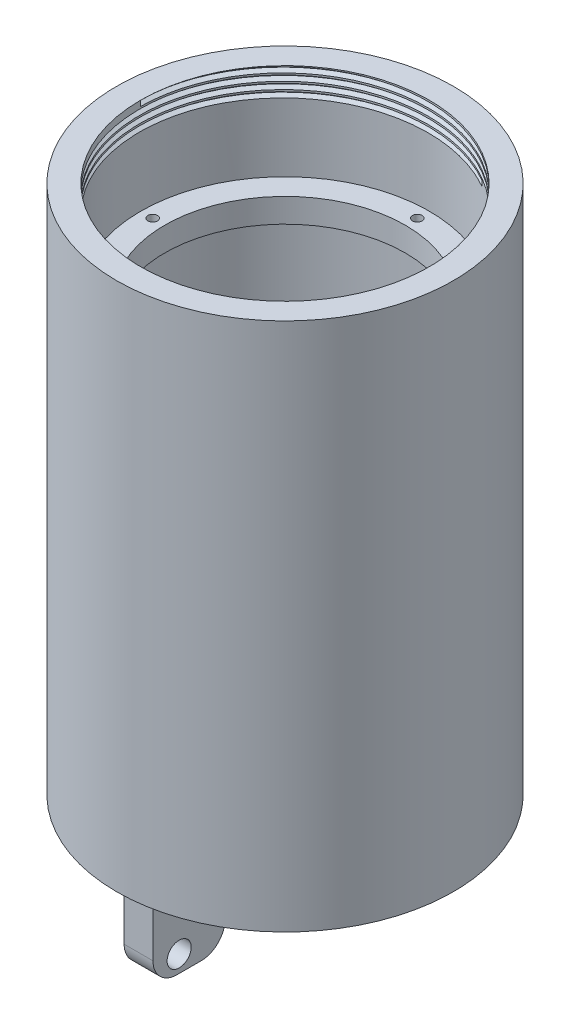
SolidWorks part; units mm, degrees
ref_plane "Front Plane" through (0, 0, 0) normal (0, 0, 1) x (1, 0, 0)
ref_plane "Top Plane" through (0, 0, 0) normal (0, 1, 0) x (1, 0, 0)
ref_plane "Right Plane" through (0, 0, 0) normal (1, 0, 0) x (0, 0, -1)
sketch "Sketch5" plane through (0, 0, 0) normal (0, 1, 0) x (1, 0, 0)
  circle A0 centre (0, 0) radius 30
  circle A1 centre (0, 0) radius 35
extrude "Boss-Extrude1" add sketch "Sketch5" along normal blind 110
sketch "Sketch15" plane through (0, 0, 0) normal (0, -1, 0) x (1, 0, 0)
  circle A0 centre (0, 0) radius 35
extrude "Boss-Extrude10" add sketch "Sketch15" against normal blind 7
sketch "Sketch16" plane through (0, 7, 0) normal (0, 1, 0) x (1, 0, 0)
  circle A0 centre (16, -15) radius 2
  circle A1 centre (16, 15) radius 2
  circle A2 centre (-16, 15) radius 2
  circle A3 centre (-16, -15) radius 2
  point P0 (0, 0)
extrude "Cut-Extrude7" cut sketch "Sketch16" against normal blind 5 contours A2
extrude "Cut-Extrude8" cut sketch "Sketch16<3>" against normal blind 5 contours A1
sketch "Sketch16<3>" plane through (0, 7, 0) normal (0, 1, 0) x (1, 0, 0) same geometry as "Sketch16"
extrude "Cut-Extrude9" cut sketch "Sketch16<4>" against normal blind 5 contours A0
sketch "Sketch16<4>" plane through (0, 7, 0) normal (0, 1, 0) x (1, 0, 0) same geometry as "Sketch16"
extrude "Cut-Extrude10" cut sketch "Sketch16<5>" against normal blind 5 contours A3
sketch "Sketch16<5>" plane through (0, 7, 0) normal (0, 1, 0) x (1, 0, 0) same geometry as "Sketch16"
sketch "Sketch17" plane through (0, 7, 0) normal (0, 1, 0) x (1, 0, 0)
  circle A0 centre (0, 0) radius 4.5
extrude "Cut-Extrude11" cut sketch "Sketch17" against normal through all
thread "Thread1" pitch 0.7 method cut profile "Thread Profile1" start angle 0, offset 0, length 5, pitch 0.7, diameter 4
ref_plane "Plane2" through (18, 2, -15) normal (0, 0, 1) x (1, 0, 0)
sketch "Thread Profile1" plane through (18, 2, -15) normal (0, 0, 1) x (1, 0, 0)
  line L0 (0, 0) -> (0, 0.7) construction
  line L1 (0, 0) -> (0.3789, 0.2187)
  line L2 (0.3789, 0.2187) -> (0.3789, 0.3062)
  line L3 (0.3789, 0.3062) -> (0, 0.525)
  line L4 (0.3789, 0.2625) -> (0, 0.2625) construction
  line L11 (0, 0) -> (0, 0.525)
  point P2 (0, 0)
  dimension "Pitch" = 0.7
  dimension "Profile_Angle" = 60
  dimension "Profile_Land" = 0.0875
  dimension "Profile_Height" = 0.3789
thread "Thread2" pitch 0.7 method cut profile "Thread Profile2" start angle 0, offset 0, length 5, pitch 0.7, diameter 4
ref_plane "Plane3" through (-14, 2, -15) normal (0, 0, 1) x (1, 0, 0)
sketch "Thread Profile2" plane through (-14, 2, -15) normal (0, 0, 1) x (1, 0, 0)
  line L0 (0, 0) -> (0, 0.7) construction
  line L1 (0, 0) -> (0.3789, 0.2187)
  line L2 (0.3789, 0.2187) -> (0.3789, 0.3062)
  line L3 (0.3789, 0.3062) -> (0, 0.525)
  line L4 (0.3789, 0.2625) -> (0, 0.2625) construction
  line L11 (0, 0) -> (0, 0.525)
  point P2 (0, 0)
  dimension "Pitch" = 0.7
  dimension "Profile_Angle" = 60
  dimension "Profile_Land" = 0.0875
  dimension "Profile_Height" = 0.3789
thread "Thread3" pitch 0.7 method cut profile "Thread Profile3" start angle 0, offset 0, length 5, pitch 0.7, diameter 4
ref_plane "Plane4" through (-14, 2, 15) normal (0, 0, 1) x (1, 0, 0)
sketch "Thread Profile3" plane through (-14, 2, 15) normal (0, 0, 1) x (1, 0, 0)
  line L0 (0, 0) -> (0, 0.7) construction
  line L1 (0, 0) -> (0.3789, 0.2187)
  line L2 (0.3789, 0.2187) -> (0.3789, 0.3062)
  line L3 (0.3789, 0.3062) -> (0, 0.525)
  line L4 (0.3789, 0.2625) -> (0, 0.2625) construction
  line L11 (0, 0) -> (0, 0.525)
  point P2 (0, 0)
  dimension "Pitch" = 0.7
  dimension "Profile_Angle" = 60
  dimension "Profile_Land" = 0.0875
  dimension "Profile_Height" = 0.3789
thread "Thread4" pitch 0.7 method cut profile "Thread Profile4" start angle 0, offset 0, length 5, pitch 0.7, diameter 4
ref_plane "Plane5" through (18, 2, 15) normal (0, 0, 1) x (1, 0, 0)
sketch "Thread Profile4" plane through (18, 2, 15) normal (0, 0, 1) x (1, 0, 0)
  line L0 (0, 0) -> (0, 0.7) construction
  line L1 (0, 0) -> (0.3789, 0.2187)
  line L2 (0.3789, 0.2187) -> (0.3789, 0.3062)
  line L3 (0.3789, 0.3062) -> (0, 0.525)
  line L4 (0.3789, 0.2625) -> (0, 0.2625) construction
  line L11 (0, 0) -> (0, 0.525)
  point P2 (0, 0)
  dimension "Pitch" = 0.7
  dimension "Profile_Angle" = 60
  dimension "Profile_Land" = 0.0875
  dimension "Profile_Height" = 0.3789
sketch "Sketch29" plane through (0, 0, 0) normal (0, -1, 0) x (1, 0, 0)
  line L0 (0, 0) -> (0, 35)
  line L1 (0, 0) -> (0, 22.9431)
  line L7 (-3, 15.4499) -> (3, 15.4499)
  line L8 (-3, 15.4499) -> (-3, 30.4363)
  line L9 (-3, 30.4363) -> (3, 30.4363)
  line L10 (3, 15.4499) -> (3, 30.4363)
  line L11 (-3, 15.4499) -> (3, 30.4363) construction
  line L12 (-3, 30.4363) -> (3, 15.4499) construction
  circle A0 centre (0, 0) radius 35 construction
extrude "Boss-Extrude13" add sketch "Sketch29" along normal blind 18.21 contours L7 L10 L9 L0 L1 | L9 L8 L7 L1 L0 region at (-1.5, 0, 22.9431) region at (1.5, 0, 22.9431)
fillet "Fillet1" radius 5 2 edges at (0, -18.21, 15.4499) (0, -18.21, 30.4363)
thread "Thread6" pitch 1.5 method cut profile "Thread Profile6" start angle 0, offset 0, length 5, pitch 1.5, diameter 60
ref_plane "Plane7" through (-30, 110, 0) normal (0, 0, 1) x (-1, 0, 0)
sketch "Thread Profile6" plane through (-30, 110, 0) normal (0, 0, 1) x (-1, 0, 0)
  line L0 (0, 0) -> (0, 1.5) construction
  line L1 (0, 0) -> (0.8119, 0.4687)
  line L2 (0.8119, 0.4687) -> (0.8119, 0.6562)
  line L3 (0.8119, 0.6562) -> (0, 1.125)
  line L4 (0.8119, 0.5625) -> (0, 0.5625) construction
  line L11 (0, 0) -> (0, 1.125)
  point P2 (0, 0)
  dimension "Pitch" = 1.5
  dimension "Profile_Angle" = 60
  dimension "Profile_Land" = 0.1875
  dimension "Profile_Height" = 0.8119
sketch "Sketch33" plane through (0, 7, 0) normal (0, 1, 0) x (1, 0, 0)
  circle A0 centre (20.68, 0) radius 3
  circle A1 centre (-23.2049, 0) radius 3
extrude "Cut-Extrude17" cut sketch "Sketch33" against normal blind 10 contours A1 | A0 region at (20.68, 7, 0) region at (-23.2049, 7, 0)
sketch "Sketch34" plane through (0, 0, 0) normal (0, 0, 1) x (1, 0, 0)
  line L0 (0, 0) -> (0, 85)
  line L6 (25, 85) -> (30, 85)
  line L7 (30, 85) -> (30, 90)
  line L8 (30, 90) -> (25, 90)
  line L9 (25, 90) -> (25, 85)
sketch "Sketch35" plane through (0, 0, 0) normal (0, 0, 1) x (1, 0, 0)
  line L0 (0, 0) -> (0, 60)
  line L1 (0, 0) -> (0, 85) construction
  line L2 (25, 65) -> (25, 60)
  line L3 (25, 60) -> (30, 60)
  line L12 (30, 60) -> (30, 65)
  line L13 (30, 65) -> (25, 65)
revolve "Revolve4" add sketch "Sketch35" angle 360 about L0
revolve "Revolve5" add sketch "Sketch34" angle 360 about L0
sketch "Sketch38" plane through (0, 65, 0) normal (0, 1, 0) x (1, 0, 0)
  line L0 (0, 0) -> (0, 27.5)
  line L1 (0, 0) -> (0, -27.5)
  line L2 (0, 0) -> (27.5, 0)
  line L4 (25, 0) -> (30, 0) construction
  line L5 (0, 0) -> (-27.5, 0)
  circle A0 centre (0, 27.5) radius 1
  circle A1 centre (27.5, 0) radius 1
  circle A2 centre (0, -27.5) radius 1
  circle A3 centre (-27.5, 0) radius 1
extrude "Cut-Extrude20" cut sketch "Sketch38" against normal blind 5 contours A0 | A1 | A2 | A3
sketch "Sketch39" plane through (0, 90, 0) normal (0, 1, 0) x (1, 0, 0)
  line L0 (0, 0) -> (27.5, 0)
  line L1 (0, 0) -> (-27.5, 0)
  line L2 (0, 0) -> (0, 27.5)
  line L3 (0, 0) -> (0, -27.5)
  circle A0 centre (0, 27.5) radius 1
  circle A1 centre (27.5, 0) radius 1
  circle A2 centre (0, -27.5) radius 1
  circle A3 centre (-27.5, 0) radius 1
extrude "Cut-Extrude22" cut sketch "Sketch39" against normal blind 5 contours A0 | A1 | A2 | A3
sketch "Sketch43" plane through (-3, 0, 0) normal (-1, 0, 0) x (0, 0, 1)
  circle A0 centre (24.9963, -14.71) radius 2.5
extrude "Cut-Extrude27" cut sketch "Sketch43" against normal through all
sketch "Sketch44" plane through (0, 0, 0) normal (0, -1, 0) x (1, 0, 0)
  circle A0 centre (0, 0) radius 6
extrude "Cut-Extrude28" cut sketch "Sketch44" against normal blind 3
